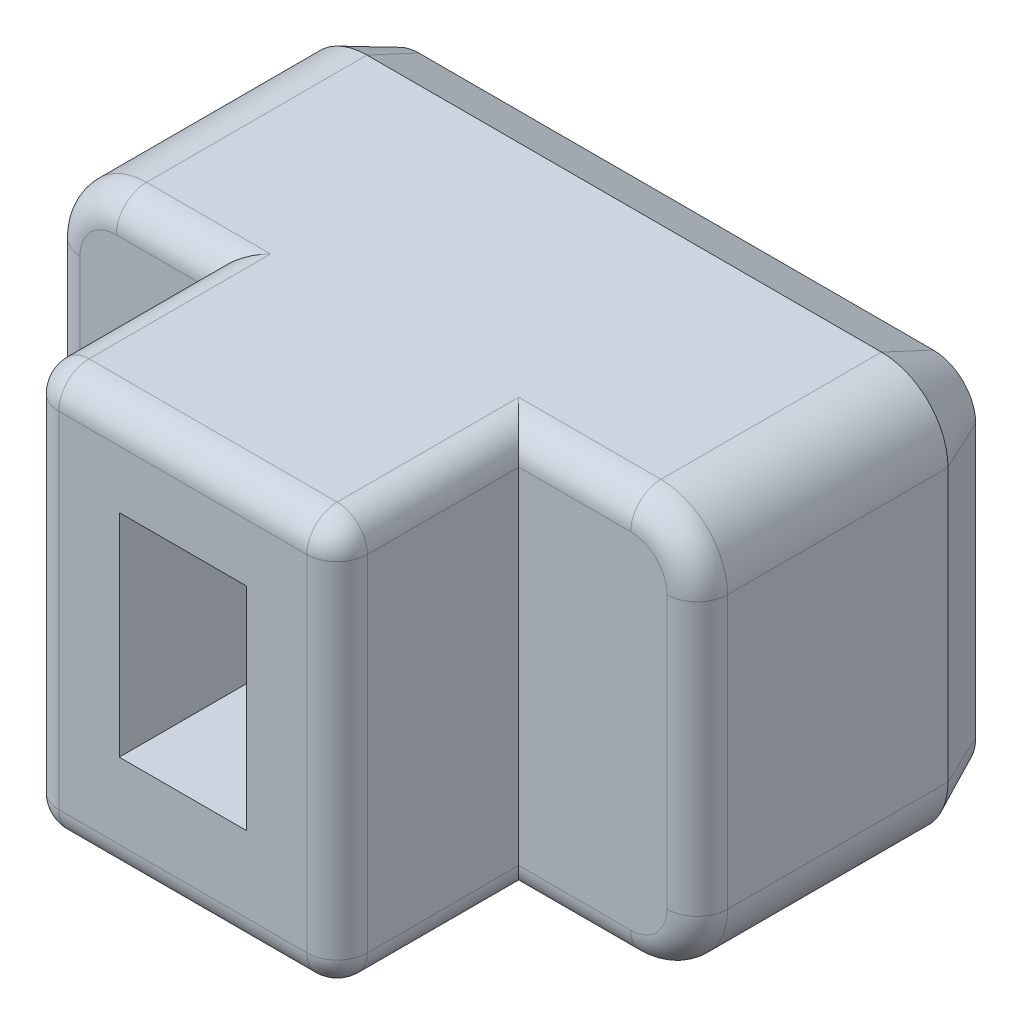
SolidWorks part; units mm, degrees
ref_plane "Plan de face" through (0, 0, 0) normal (0, 0, 1) x (1, 0, 0)
ref_plane "Plan de dessus" through (0, 0, 0) normal (0, 1, 0) x (1, 0, 0)
ref_plane "Plan de droite" through (0, 0, 0) normal (1, 0, 0) x (0, 0, -1)
sketch "Esquisse2" plane through (0, 0, 0) normal (0, 0, 1) x (1, 0, 0)
  line L1 (1.1, 0) -> (9.6, 0)
  line L2 (0, 1.1) -> (0, 5.6)
  line L3 (1.1, 6.7) -> (9.6, 6.7)
  line L4 (10.7, 1.1) -> (10.7, 5.6)
  arc A0 (9.6, 6.7) -> (10.7, 5.6) centre (9.6, 5.6) cw
  arc A1 (9.6, 0) -> (10.7, 1.1) centre (9.6, 1.1) ccw
  arc A2 (1.1, 0) -> (0, 1.1) centre (1.1, 1.1) cw
  arc A3 (0, 5.6) -> (1.1, 6.7) centre (1.1, 5.6) cw
  point P7 (10.7, 6.7)
  point P12 (0, 0)
  point P15 (0, 6.7)
  dimension "D3" = 1.1
  dimension "D1" = 10.7
  dimension "D2" = 6.7
extrude "Boss.-Extru.1" add sketch "Esquisse2" along normal blind 8
sketch "Esquisse3" plane through (0, 0, 8) normal (0, 0, 1) x (1, 0, 0)
  line L0 (0, 5.6) -> (0, 1.1) construction
  line L1 (4.15, 5.25) -> (6.25, 5.25)
  line L2 (4.15, 5.25) -> (4.15, 1.75)
  line L3 (4.15, 1.75) -> (6.25, 1.75)
  line L4 (6.25, 5.25) -> (6.25, 1.75)
  line L5 (10.7, 1.1) -> (10.7, 5.6) construction
  line L6 (9.6, 6.7) -> (1.1, 6.7) construction
  line L7 (1.1, 0) -> (9.6, 0) construction
  dimension "D1" = 2.1
  dimension "D2" = 3.5
  dimension "D3" = 4.15
  dimension "D4" = 4.45
  dimension "D5" = 1.45
  dimension "D6" = 1.75
extrude "Enlèv. mat.-Extru.1" cut sketch "Esquisse3" against normal blind 3
sketch "Esquisse4" plane through (0, 0, 8) normal (0, 0, 1) x (1, 0, 0)
  line L0 (2.65, 6.7) -> (2.65, 0)
  line L1 (9.6, 6.7) -> (1.1, 6.7) construction
  line L2 (1.1, 0) -> (9.6, 0) construction
  line L3 (2.65, 0) -> (7.75, 0)
  line L4 (7.75, 0) -> (7.75, 6.7)
  line L5 (7.75, 6.7) -> (2.65, 6.7)
  line L6 (4.15, 5.25) -> (4.15, 1.75) construction
  line L7 (6.25, 1.75) -> (6.25, 5.25) construction
  dimension "D1" = 1.5
  dimension "D2" = 1.5
extrude "Enlèv. mat.-Extru.2" cut sketch "Esquisse4" against normal blind 3 flip side to cut
fillet "Congé1" radius 0.5 18 edges at (8.675, 0, 5) (10.3778, 0.3222, 5) (10.7, 3.35, 5) (10.3778, 6.3778, 5) (1.875, 6.7, 5) (0.3222, 6.3778, 5) (1.875, 0, 5) (0.3222, 0.3222, 5) (7.75, 6.7, 6.5) (2.65, 6.7, 6.5) (7.75, 0, 6.5) (2.65, 0, 6.5) (2.65, 3.35, 8) (5.2, 6.7, 8) (7.75, 3.35, 8) (5.2, 0, 8) (8.675, 6.7, 5) (0, 3.35, 5)
chamfer "Chanfrein1" distance 0.4 angle 65 8 edges at (5.35, 0, 0) (10.3778, 0.3222, 0) (0.3222, 0.3222, 0) (10.7, 3.35, 0) (0, 3.35, 0) (10.3778, 6.3778, 0) (0.3222, 6.3778, 0) (5.35, 6.7, 0) first distance on face at (5.35, 3.35, 0)
ref_plane "Plan1" through (0, 0, 0.2) normal (0, 0, 1) x (1, 0, 0)
sketch "Esquisse5" plane through (0, 0, 0.2) normal (0, 0, 1) x (1, 0, 0)
  line L0 (-0.9378, 5.3566) -> (11.6517, 5.3566) construction
  text T0 "APR" font "Century Gothic" height 4
extrude "Enlèv. mat.-Extru.3" cut sketch "Esquisse5" against normal blind 0.3
extrude "Boss.-Extru.2" add sketch "Esquisse5<3>" against normal blind 0.2 from offset 0.2 offset against normal yes
sketch "Esquisse5<3>" plane through (0, 0, 0.2) normal (0, 0, 1) x (1, 0, 0) same geometry as "Esquisse5"
